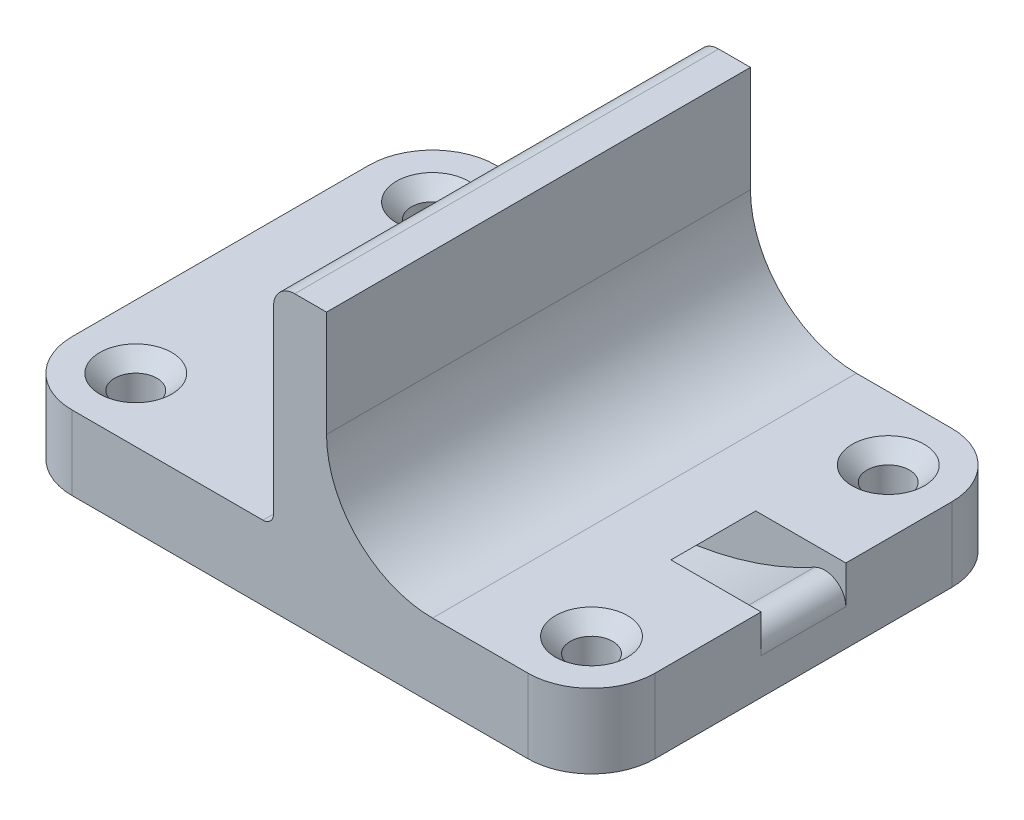
SolidWorks part; units mm, degrees
ref_plane "Front Plane" through (0, 0, 0) normal (0, 0, 1) x (1, 0, 0)
ref_plane "Top Plane" through (0, 0, 0) normal (0, 1, 0) x (1, 0, 0)
ref_plane "Right Plane" through (0, 0, 0) normal (1, 0, 0) x (0, 0, -1)
sketch "Sketch1" plane through (0, 0, 0) normal (0, 0, 1) x (1, 0, 0)
  line L0 (0, 0) -> (0, 20)
  line L1 (0, 20) -> (-5, 20)
  line L2 (-5, 20) -> (-5, 0)
  line L3 (-5, 0) -> (-30, 0)
  line L4 (-30, 0) -> (-30, -7)
  line L5 (-30, -7) -> (25, -7)
  line L6 (25, -7) -> (25, 0)
  line L7 (25, 0) -> (0, 0)
  dimension "D1" = 20
  dimension "D2" = 25
  dimension "D3" = 5
  dimension "D4" = 7
  dimension "D5" = 25
extrude "Boss-Extrude1" add sketch "Sketch1" along normal blind 40
ref_plane "Plane1" through (0, 0, 20) normal (0, 0, 1) x (1, 0, 0)
sketch "Sketch3" plane through (0, 0, 40) normal (0, 0, 1) x (1, 0, 0)
  line L0 (-30, -7) -> (25, -7) construction
  circle A0 centre (5.7488, 27.8841) radius 29.8841
  circle A1 centre (5.7488, 27.8841) radius 33.8841
  point P6 (5.7488, -6)
  point P7 (10.0544, 55.6588)
  dimension "D1" = 4
  dimension "D2" = 1
extrude "Cut-Extrude1" cut sketch "Sketch3" against normal blind 4 and the other way blind 4 from surface starting at plane "Plane1"
fillet "Fillet1" radius 2 1 edges at (-5, 0, 20)
fillet "Fillet2" radius 2 1 edges at (-5, 20, 20)
fillet "Fillet3" radius 2 1 edges at (25, 0, 20) tangent propagation no
sketch "Sketch4" plane through (0, 0, 0) normal (0, 1, 0) x (1, 0, 0)
  line L0 (-24, -34) -> (-24, -40) construction
  line L1 (19, -6) -> (25, -6) construction
  line L2 (25, -16) -> (25, 0) construction
  line L3 (-5, -40) -> (-30, -40) construction
  line L4 (-24, -34) -> (-30, -34) construction
  line L5 (-30, -40) -> (-30, 0) construction
  line L6 (19, -34) -> (19, -40) construction
  line L7 (25, -40) -> (0, -40) construction
  line L8 (19, -34) -> (25, -34) construction
  line L9 (25, -40) -> (25, -24) construction
  line L10 (19, -6) -> (19, 0) construction
  line L11 (25, 0) -> (0, 0) construction
  circle A0 centre (-24, -6) radius 2
  circle A1 centre (-24, -34) radius 2
  circle A2 centre (19, -34) radius 2
  circle A3 centre (19, -6) radius 2
  point P8 (-28.7175, -6.2825)
  dimension "D2" = 4
  dimension "D1" = 6
extrude "Cut-Extrude2" cut sketch "Sketch4" against normal up to surface (7 mm away) up to face at (-2.5, -7, 20)
chamfer "Chamfer1" distance 1.4 angle 45 4 edges at (17, 0, 6) (17, 0, 34) (-26, 0, 34) (-26, 0, 6)
fillet "Fillet4" radius 1 2 edges at (-5, 0, 32) (-5, 0, 8) tangent propagation no
fillet "Fillet5" radius 10 1 edges at (0, 0, 20)
fillet "Fillet6" radius 6 4 edges at (25, -3.5, 0) (-30, -3.5, 0) (-30, -3.5, 40) (25, -3.5, 40)
